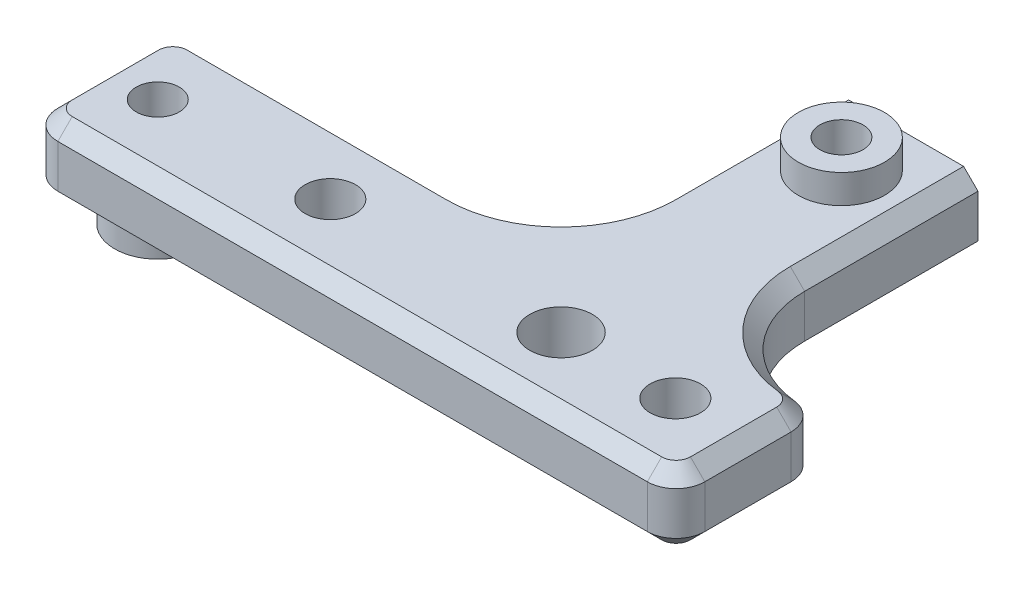
SolidWorks part; units mm, degrees
ref_plane "Front Plane" through (0, 0, 0) normal (0, 0, 1) x (1, 0, 0)
ref_plane "Top Plane" through (0, 0, 0) normal (0, 1, 0) x (1, 0, 0)
ref_plane "Right Plane" through (0, 0, 0) normal (1, 0, 0) x (0, 0, -1)
sketch "Sketch1" plane through (0, 0, 0) normal (0, 1, 0) x (1, 0, 0)
  line L1 (-22.5, 5) -> (22.5, 5)
  line L2 (-22.5, 5) -> (-22.5, -5)
  line L3 (-22.5, -5) -> (22.5, -5)
  line L4 (22.5, 5) -> (22.5, -5)
  line L5 (-22.5, 5) -> (22.5, -5) construction
  line L6 (-22.5, -5) -> (22.5, 5) construction
  point P0 (0, 0)
  dimension "D1" = 45
  dimension "D2" = 10
extrude "Boss-Extrude1" add sketch "Sketch1" along normal blind 5
sketch "Sketch3" plane through (0, 5, 0) normal (0, 1, 0) x (1, 0, 0)
  line L0 (-22.5, 5) -> (-22.5, -5) construction
  circle A0 centre (-18.55, 0) radius 1.5
  circle A1 centre (9.5, 0) radius 2.175
  circle A3 centre (-6.55, 0) radius 1.75
  circle A4 centre (17.45, 0) radius 1.75
  dimension "D3" = 3
  dimension "D4" = 4.35
  dimension "D7" = 3.5
  dimension "D9" = 3.5
  dimension "D1" = 28.05
  dimension "D2" = 3.95
  dimension "D8" = 12
  dimension "D10" = 24
extrude "Cut-Extrude1" cut sketch "Sketch3" against normal blind 7
fillet "Fillet1" radius 2 4 edges at (22.5, 2.5, -5) (-22.5, 2.5, -5) (22.5, 2.5, 5) (-22.5, 2.5, 5)
sketch "Sketch4" plane through (0, 0, 0) normal (0, -1, 0) x (1, 0, 0)
  circle A0 centre (-18.55, 0) radius 1.5
  circle A1 centre (-18.55, 0) radius 3
  dimension "D1" = 1.5
extrude "Boss-Extrude2" add sketch "Sketch4" along normal blind 2.5
sketch "Sketch5" plane through (0, 0, -5) normal (0, 0, -1) x (-1, 0, 0)
  line L0 (-20.5, 5) -> (20.5, 5) construction
  line L1 (-14.5, 5) -> (-4.5, 5)
  line L2 (-14.5, 5) -> (-14.5, 0)
  line L3 (-14.5, 0) -> (-4.5, 0)
  line L4 (-4.5, 5) -> (-4.5, 0)
  line L5 (-20.5, 0) -> (20.5, 0) construction
  line L6 (-22.5, 0) -> (-22.5, 5) construction
  line L7 (22.5, 5) -> (22.5, 0) construction
  dimension "D1" = 10
  dimension "D2" = 8
  dimension "D3" = 27
extrude "Boss-Extrude3" add sketch "Sketch5" along normal blind 19
sketch "Sketch6" plane through (0, 5, 0) normal (0, 1, 0) x (1, 0, 0)
  line L0 (14.5, 24) -> (14.5, 5) construction
  line L1 (4.5, 24) -> (14.5, 24) construction
  circle A0 centre (9.5, 19.5) radius 1.5
  dimension "D2" = 3
  dimension "D1" = 5
  dimension "D3" = 4.5
extrude "Cut-Extrude2" cut sketch "Sketch6" against normal blind 10
sketch "Sketch7" plane through (0, 5, 0) normal (0, 1, 0) x (1, 0, 0)
  circle A0 centre (9.5, 19.5) radius 3
  circle A1 centre (9.5, 19.5) radius 1.5
  dimension "D1" = 1.5
extrude "Boss-Extrude4" add sketch "Sketch7" along normal blind 2
fillet "Fillet2" radius 7 2 edges at (4.5, 2.5, -5) (14.5, 2.5, -5)
chamfer "Chamfer1" distance 1 angle 45 24 edges at (4.5, 0, -18) (2.4497, 0, -7.0503) (-21.9142, 0, -4.4142) (-22.5, 0, 0) (-21.9142, 0, 4.4142) (0, 0, 5) (21.9142, 0, 4.4142) (22.5, 0, 0) (14.5, 0, -17.9721) (21.9907, 0, -4.3333) (16.2825, 0, -7.2776) (-11.5, 0, -5) (4.5, 5, -18) (2.4497, 5, -7.0503) (-21.9142, 5, -4.4142) (-22.5, 5, 0) (14.5, 5, -17.9721) (-21.9142, 5, 4.4142) (16.2825, 5, -7.2776) (0, 5, 5) (-11.5, 5, -5) (21.9142, 5, 4.4142) (21.9907, 5, -4.3333) (22.5, 5, 0)
